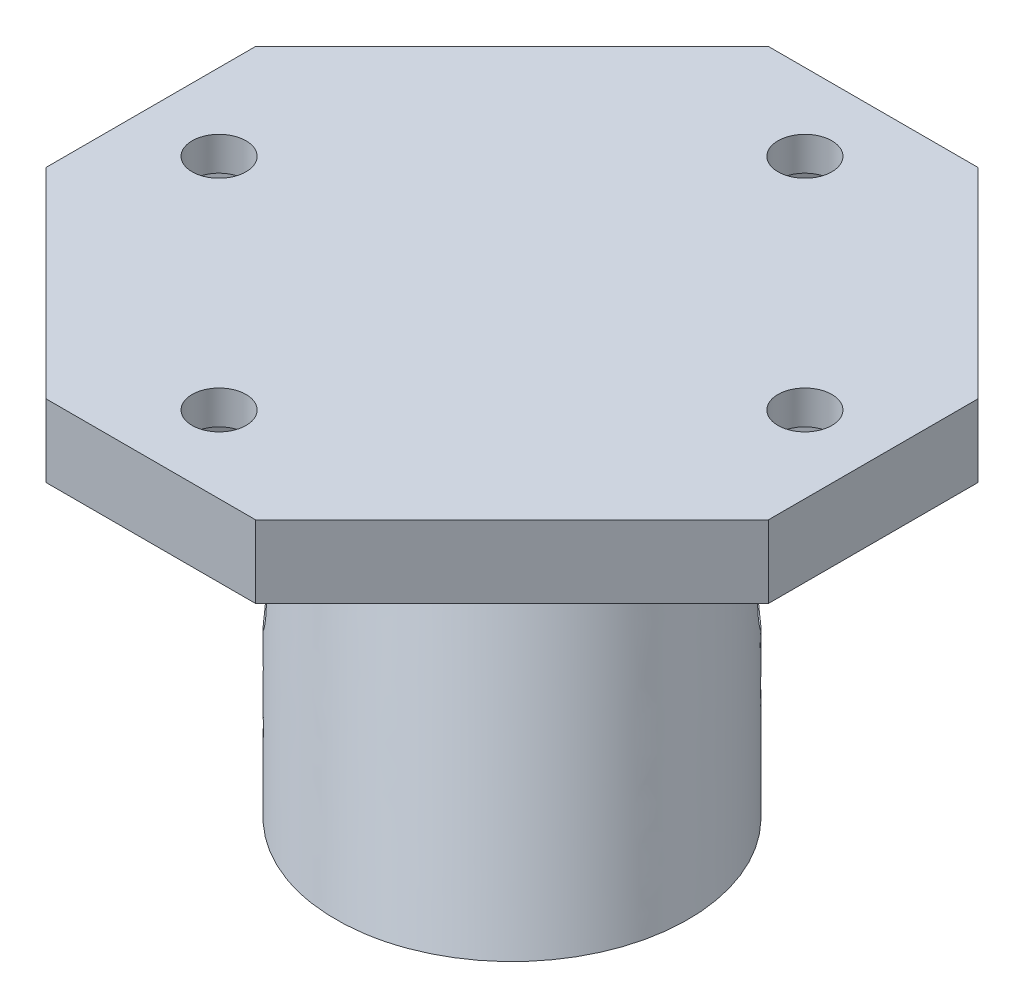
SolidWorks part; units mm, degrees
ref_plane "Front Plane" through (0, 0, 0) normal (0, 0, 1) x (1, 0, 0)
ref_plane "Top Plane" through (0, 0, 0) normal (0, 1, 0) x (1, 0, 0)
ref_plane "Right Plane" through (0, 0, 0) normal (1, 0, 0) x (0, 0, -1)
sketch "Sketch1" plane through (0, 0, 0) normal (0, 1, 0) x (1, 0, 0)
  line L0 (-40.3039, 15.5552) -> (-15.5552, 40.3039)
  line L1 (-40.3039, -40.3039) -> (40.3039, -40.3039) construction
  line L2 (-40.3039, -40.3039) -> (-40.3039, 40.3039) construction
  line L3 (-40.3039, 40.3039) -> (40.3039, 40.3039) construction
  line L4 (40.3039, -40.3039) -> (40.3039, 40.3039) construction
  line L5 (-40.3039, -40.3039) -> (40.3039, 40.3039) construction
  line L6 (-40.3039, 40.3039) -> (40.3039, -40.3039) construction
  line L7 (-27.9296, 27.9296) -> (2.476, -2.476) construction
  line L8 (-11.6661, -16.6182) -> (16.6182, 11.6661) construction
  line L9 (-11.6661, -16.6182) -> (-32.8793, 4.5951) construction
  line L10 (16.6182, 11.6661) -> (-4.5951, 32.8793) construction
  line L11 (-40.3039, 15.5552) -> (-40.3039, -4.6948)
  line L12 (-15.5552, 40.3039) -> (4.6948, 40.3039)
  line L13 (24.0428, 0.706) -> (24.0428, 20.956)
  line L14 (-0.706, -24.0428) -> (-20.956, -24.0428)
  line L15 (-32.8793, 4.5951) -> (-4.5951, 32.8793) construction
  line L16 (-18.7372, 18.7372) -> (11.6684, -11.6684) construction
  line L17 (-0.706, -24.0428) -> (24.0428, 0.706)
  line L18 (-40.3039, -4.6948) -> (-20.956, -24.0428)
  line L19 (4.6948, 40.3039) -> (24.0428, 20.956)
  circle A0 centre (-11.6661, -16.6182) radius 2.6
  circle A1 centre (16.6182, 11.6661) radius 2.6
  circle A2 centre (-4.5951, 32.8793) radius 2.6
  circle A3 centre (-32.8793, 4.5951) radius 2.6
  point P0 (0, 0)
  point P13 (2.476, -2.476)
  point P28 (11.6684, -11.6684)
  dimension "D6" = 5.2
  dimension "D1" = 135
  dimension "D2" = 35
  dimension "D3" = 43
  dimension "D4" = 40
  dimension "D5" = 30
  dimension "D7" = 20.25
  dimension "D8" = 20.25
  dimension "D9" = 43
  dimension "D10" = 35
  dimension "D11" = 20.25
  dimension "D12" = 20.25
extrude "Boss-Extrude1" add sketch "Sketch1" along normal blind 7
sketch "Sketch2" plane through (0, 0, 0) normal (0, -1, 0) x (1, 0, 0)
  line L0 (-40.3039, -15.5552) -> (-40.3039, 4.6948) construction
  line L1 (-36.9793, -2.2279) -> (-36.9793, -6.9622)
  line L2 (-36.9793, -6.9622) -> (-32.8793, -9.3293)
  line L3 (-32.8793, -9.3293) -> (-28.7793, -6.9622)
  line L4 (-28.7793, -6.9622) -> (-28.7793, -2.2279)
  line L5 (-28.7793, -2.2279) -> (-32.8793, 0.1392)
  line L6 (-32.8793, 0.1392) -> (-36.9793, -2.2279)
  line L7 (-15.5552, -40.3039) -> (4.6948, -40.3039) construction
  line L8 (-14.0333, 12.5182) -> (-9.299, 12.5182)
  line L9 (-9.299, 12.5182) -> (-6.9318, 16.6182)
  line L10 (-6.9318, 16.6182) -> (-9.299, 20.7182)
  line L11 (-9.299, 20.7182) -> (-14.0333, 20.7182)
  line L12 (-14.0333, 20.7182) -> (-16.4004, 16.6182)
  line L13 (-16.4004, 16.6182) -> (-14.0333, 12.5182)
  line L14 (16.6182, -6.9318) -> (12.5182, -9.299)
  line L15 (12.5182, -9.299) -> (12.5182, -14.0333)
  line L16 (12.5182, -14.0333) -> (16.6182, -16.4004)
  line L17 (16.6182, -16.4004) -> (20.7182, -14.0333)
  line L18 (20.7182, -14.0333) -> (20.7182, -9.299)
  line L19 (20.7182, -9.299) -> (16.6182, -6.9318)
  line L20 (-2.2279, -28.7793) -> (-6.9622, -28.7793)
  line L21 (-6.9622, -28.7793) -> (-9.3293, -32.8793)
  line L22 (-9.3293, -32.8793) -> (-6.9622, -36.9793)
  line L23 (-6.9622, -36.9793) -> (-2.2279, -36.9793)
  line L24 (-2.2279, -36.9793) -> (0.1392, -32.8793)
  line L25 (0.1392, -32.8793) -> (-2.2279, -28.7793)
  line L26 (24.0428, -0.706) -> (24.0428, -20.956) construction
  line L27 (-0.706, 24.0428) -> (-20.956, 24.0428) construction
  circle A0 centre (-32.8793, -4.5951) radius 4.1 construction
  circle A1 centre (-11.6661, 16.6182) radius 4.1 construction
  circle A2 centre (16.6182, -11.6661) radius 4.1 construction
  circle A3 centre (-4.5951, -32.8793) radius 4.1 construction
  dimension "D1" = 8.2
extrude "Cut-Extrude1" cut sketch "Sketch2" against normal blind 3.75
sketch "Sketch3" plane through (0, 0, 0) normal (0, -1, 0) x (1, 0, 0)
  line L0 (-30.63, 14.3688) -> (14.3688, -30.63) construction
  line L1 (-40.3039, 4.6948) -> (-20.956, 24.0428) construction
  line L2 (24.0428, -20.956) -> (4.6948, -40.3039) construction
  line L3 (-8.1306, -8.1306) -> (11.6684, 11.6684) construction
  line L4 (-0.706, 24.0428) -> (24.0428, -0.706) construction
  circle A0 centre (-8.1306, -8.1306) radius 14
  circle A1 centre (-8.1306, -8.1306) radius 17
  dimension "D1" = 28
  dimension "D2" = 3
ref_plane "Plane1" through (0, -25, 0) normal (0, -1, 0) x (-1, 0, 0)
ref_plane "Plane2" through (0, 0, 0) normal (0.7071, 0, -0.7071) x (-0.7071, 0, -0.7071)
sketch "Sketch5" plane through (0, -25, 0) normal (0, -1, 0) x (-1, 0, 0)
  line L0 (8.1306, 8.1306) -> (-11.6684, -11.6684) construction
  point P7 (8.1306, 8.1306)
sketch "Sketch6" plane through (0, 0, 0) normal (0.7071, 0, -0.7071) x (-0.7071, 0, -0.7071)
  line L0 (-5.5016, 0) -> (28.4984, 0) construction
  line L2 (11.4984, 0) -> (-16.5016, 0) construction
  line L3 (11.4984, 0) -> (0.5793, -30)
  point P0 (11.4984, 0)
  dimension "D1" = 70
  dimension "D2" = 30
sweep "Sweep2" add profiles "Sketch3" path "Sketch6"
sketch "Sketch8" plane through (0, 0, 0) normal (0.7071, 0, -0.7071) x (-0.7071, 0, -0.7071)
  line L0 (11.4984, 0) -> (0.5793, -30) construction
  circle A0 centre (6.0388, -15) radius 2.6
  dimension "D1" = 5.2
extrude "Cut-Extrude2" cut sketch "Sketch8" against normal blind 20 and the other way blind 20
fillet "Fillet2" radius 3 1 edges at (-8.1306, 0, -25.1306)
